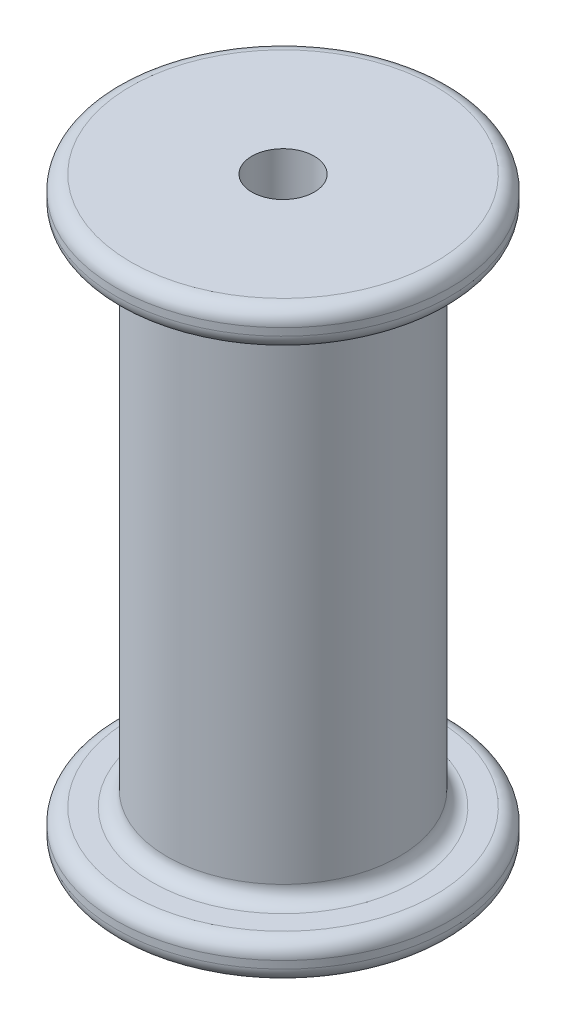
SolidWorks part; units mm, degrees
ref_plane "Front Plane" through (0, 0, 0) normal (0, 0, 1) x (1, 0, 0)
ref_plane "Top Plane" through (0, 0, 0) normal (0, 1, 0) x (1, 0, 0)
ref_plane "Right Plane" through (0, 0, 0) normal (1, 0, 0) x (0, 0, -1)
sketch "Sketch2" plane through (0, 0, 0) normal (0, 1, 0) x (1, 0, 0)
  circle A0 centre (0, 0) radius 2.667
  circle A1 centre (0, 0) radius 9.906
  dimension "D1" = 5.334
  dimension "D2" = 19.812
extrude "Boss-Extrude1" add sketch "Sketch2" along normal blind 50.038
sketch "Sketch3" plane through (0, 50.038, 0) normal (0, 1, 0) x (1, 0, 0)
  circle A0 centre (0, 0) radius 14.2875
  circle A1 centre (0, 0) radius 2.667 construction
  circle A2 centre (0, 0) radius 2.667
  dimension "D1" = 28.575
extrude "Boss-Extrude2" add sketch "Sketch3" against normal blind 3.175
extrude "Boss-Extrude3" add sketch "Sketch3<2>" along normal blind 3.175 from surface starting at face at (0, 0, 9.906)
sketch "Sketch3<2>" plane through (0, 50.038, 0) normal (0, 1, 0) x (1, 0, 0) same geometry as "Sketch3"
fillet "Fillet1" radius 1.27 6 edges at (0, 50.038, 14.2875) (0, 46.863, 14.2875) (0, 46.863, 9.906) (0, 0, 14.2875) (0, 3.175, 14.2875) (0, 3.175, 9.906)
